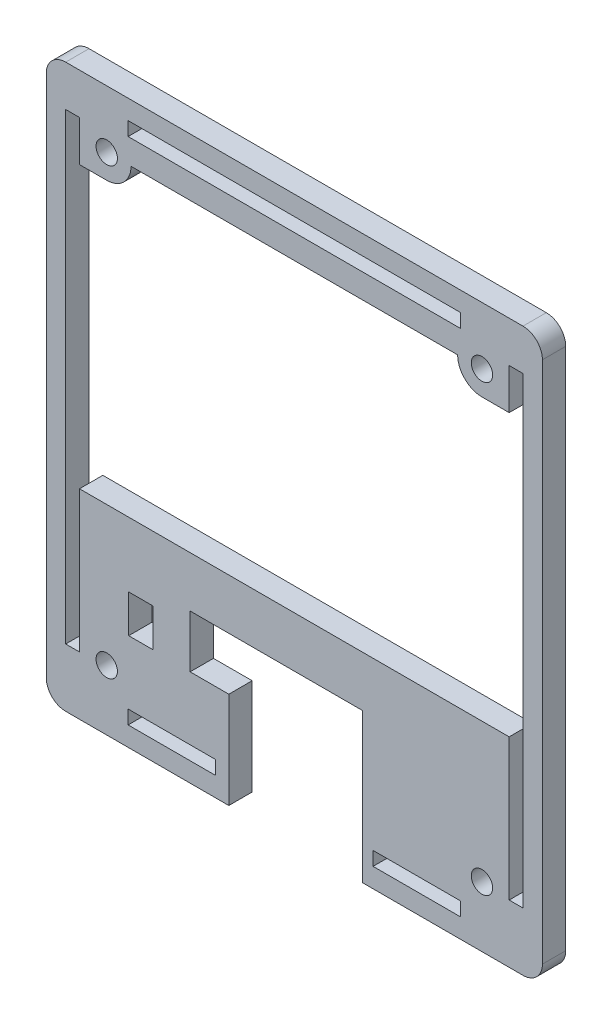
SolidWorks part; units mm, degrees
ref_plane "Front Plane" through (0, 0, 0) normal (0, 0, 1) x (1, 0, 0)
ref_plane "Top Plane" through (0, 0, 0) normal (0, 1, 0) x (1, 0, 0)
ref_plane "Right Plane" through (0, 0, 0) normal (1, 0, 0) x (0, 0, -1)
sketch "Sketch1" plane through (0, 0, 0) normal (0, 0, 1) x (1, 0, 0)
  line L0 (1.8034, 63.754) -> (0, 63.754) construction
  line L1 (0, 63.754) -> (0, 3.2766) construction
  line L2 (1.8034, 63.754) -> (1.8034, 3.2766) construction
  line L3 (1.8034, 3.2766) -> (0, 3.2766) construction
  line L4 (19.5834, -1.8034) -> (19.5834, 0) construction
  line L5 (19.5834, -1.8034) -> (8.1534, -1.8034) construction
  line L6 (8.1534, -1.8034) -> (8.1534, 0) construction
  line L7 (19.5834, 0) -> (8.1534, 0) construction
  line L8 (40.1574, -1.8034) -> (40.1574, 0) construction
  line L9 (51.5874, -1.8034) -> (40.1574, -1.8034) construction
  line L10 (51.5874, 0) -> (40.1574, 0) construction
  line L11 (51.5874, -1.8034) -> (51.5874, 0) construction
  line L12 (57.9374, 3.2766) -> (59.7408, 3.2766) construction
  line L13 (59.7408, 3.2766) -> (59.7408, 63.754) construction
  line L14 (57.9374, 3.2766) -> (57.9374, 63.754) construction
  line L15 (57.9374, 63.754) -> (59.7408, 63.754) construction
  line L16 (51.5874, 66.5734) -> (51.5874, 64.77) construction
  line L17 (8.1534, 64.77) -> (51.5874, 64.77) construction
  line L18 (8.1534, 66.5734) -> (51.5874, 66.5734) construction
  line L19 (8.1534, 66.5734) -> (8.1534, 64.77) construction
  line L20 (1.8034, 63.754) -> (0, 63.754)
  line L21 (0, 63.754) -> (0, 3.2766)
  line L22 (1.8034, 63.754) -> (1.8034, 3.2766)
  line L23 (1.8034, 3.2766) -> (0, 3.2766)
  line L24 (19.5834, -1.8034) -> (19.5834, 0)
  line L25 (19.5834, -1.8034) -> (8.1534, -1.8034)
  line L26 (8.1534, -1.8034) -> (8.1534, 0)
  line L27 (19.5834, 0) -> (8.1534, 0)
  line L28 (40.1574, -1.8034) -> (40.1574, 0)
  line L29 (51.5874, -1.8034) -> (40.1574, -1.8034)
  line L30 (51.5874, 0) -> (40.1574, 0)
  line L31 (51.5874, -1.8034) -> (51.5874, 0)
  line L32 (57.9374, 3.2766) -> (59.7408, 3.2766)
  line L33 (59.7408, 3.2766) -> (59.7408, 63.754)
  line L34 (57.9374, 3.2766) -> (57.9374, 63.754)
  line L35 (57.9374, 63.754) -> (59.7408, 63.754)
  line L36 (51.5874, 66.5734) -> (51.5874, 64.77)
  line L37 (8.1534, 64.77) -> (51.5874, 64.77)
  line L38 (8.1534, 66.5734) -> (51.5874, 66.5734)
  line L39 (8.1534, 66.5734) -> (8.1534, 64.77)
  line L40 (0, -4.3434) -> (21.3106, -4.3434)
  line L41 (38.7858, -4.3434) -> (59.7408, -4.3434)
  line L42 (62.2808, -1.8034) -> (62.2808, 69.1134)
  line L43 (-2.54, -1.8034) -> (-2.54, 69.1134)
  line L44 (-2.54, 69.1134) -> (62.2808, 69.1134)
  line L45 (5.3594, 58.42) -> (1.8034, 58.42) construction
  line L46 (54.3814, 58.42) -> (57.9374, 58.42) construction
  line L47 (5.3594, 58.42) -> (1.8034, 58.42)
  line L48 (54.3814, 58.42) -> (57.9374, 58.42)
  line L49 (8.5344, 61.595) -> (51.2064, 61.595)
  line L50 (1.8034, 3.2766) -> (1.8034, 21.7424)
  line L51 (1.8034, 21.7424) -> (57.9374, 21.7424)
  line L52 (57.9374, 21.7424) -> (57.9374, 3.2766)
  line L53 (57.9374, 3.2766) -> (57.8889, 3.3886)
  line L54 (1.8034, 21.7424) -> (1.8034, 3.2766)
  line L55 (57.9374, 21.7424) -> (57.9374, 3.2766)
  circle A0 centre (54.3814, 61.595) radius 1.397 construction
  circle A1 centre (5.3594, 61.595) radius 1.397 construction
  circle A2 centre (54.3814, 61.595) radius 1.397
  circle A3 centre (5.3594, 61.595) radius 1.397
  arc A4 (-2.54, -1.8034) -> (0, -4.3434) centre (0, -1.8034) ccw construction
  arc A5 (59.7408, -4.3434) -> (62.2808, -1.8034) centre (59.7408, -1.8034) ccw construction
  arc A6 (-2.54, -1.8034) -> (0, -4.3434) centre (0, -1.8034) ccw
  arc A7 (59.7408, -4.3434) -> (62.2808, -1.8034) centre (59.7408, -1.8034) ccw
  arc A8 (5.3594, 58.42) -> (5.3594, 64.77) centre (5.3594, 61.595) ccw construction
  arc A9 (54.3814, 64.77) -> (54.3814, 58.42) centre (54.3814, 61.595) ccw construction
  arc A10 (5.3594, 58.42) -> (5.3594, 64.77) centre (5.3594, 61.595) ccw
  arc A11 (54.3814, 64.77) -> (54.3814, 58.42) centre (54.3814, 61.595) ccw
  line B0 (8.2296, 13.2842) -> (11.4046, 13.2842)
  line B1 (8.2296, 13.2842) -> (8.2296, 8.3312)
  line B2 (11.4046, 13.2842) -> (11.4046, 8.3312)
  line B3 (8.2296, 8.3312) -> (11.4046, 8.3312)
  line B4 (16.256, 15.1384) -> (16.256, 8.255)
  line B5 (16.256, 8.255) -> (21.3106, 8.255)
  line B6 (38.7858, 15.1384) -> (16.256, 15.1384)
  line B7 (38.7858, -4.3434) -> (38.7858, 15.1384)
  line B8 (21.3106, 8.255) -> (21.3106, -4.3434)
  circle B9 centre (5.3594, 3.556) radius 1.397
  circle B10 centre (54.3814, 3.556) radius 1.397
  dimension "D1" = 4.3434
  dimension "D2" = 6.604
sketch_block_instance "Block1-1"
sketch_block "Block1"
extrude "Boss-Extrude1" add sketch "Sketch1" along normal blind 3.048 contours B8 B5 B4 B6 B7 L41 A7 L42 L44 L43 A6 L40 B10 B9 B3 B1 B0 B2 L31 L29 L28 L30 L27 L24 L25 L26 L39 L38 L36 L37 A2 A3 A11 L48 L34 L35 L33 L32 region at (-1.1033, -2.9067, 0)
fillet "Fillet1" radius 2.54 2 edges at (-2.54, 69.1134, 1.524) (62.2808, 69.1134, 1.524)
